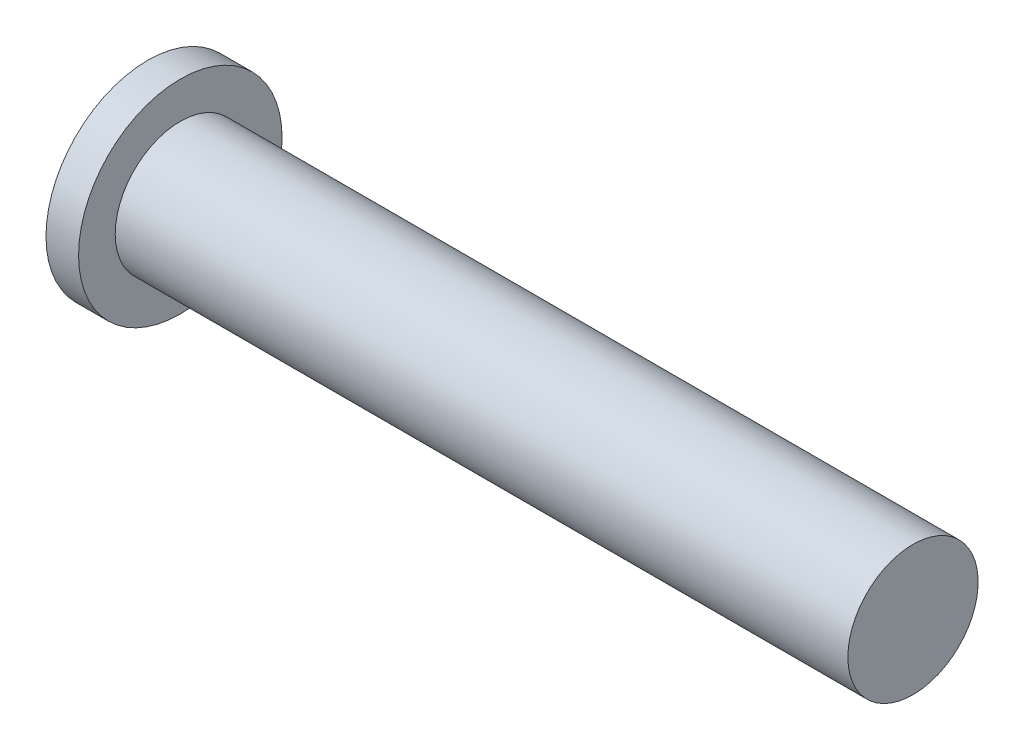
SolidWorks part; units mm, degrees
ref_plane "正面" through (0, 0, 0) normal (0, 0, 1) x (1, 0, 0)
ref_plane "平面" through (0, 0, 0) normal (0, 1, 0) x (1, 0, 0)
ref_plane "右側面" through (0, 0, 0) normal (1, 0, 0) x (0, 0, -1)
sketch "ｽｹｯﾁ1" plane through (0, 0, 0) normal (0, 1, 0) x (1, 0, 0)
  line L0 (0, 0) -> (78.1964, 0) construction
  line L1 (0, 0) -> (0, 6.25)
  line L2 (0, 6.25) -> (2, 6.25)
  line L3 (2, 6.25) -> (2, 4)
  line L4 (2, 4) -> (47, 4)
  line L5 (47, 4) -> (47, 0)
  line L6 (47, 0) -> (0, 0)
  dimension "D1" = 6.25
  dimension "D2" = 4
  dimension "D3" = 2
  dimension "D4" = 47
revolve "回転1" add sketch "ｽｹｯﾁ1" angle 360 about L0
